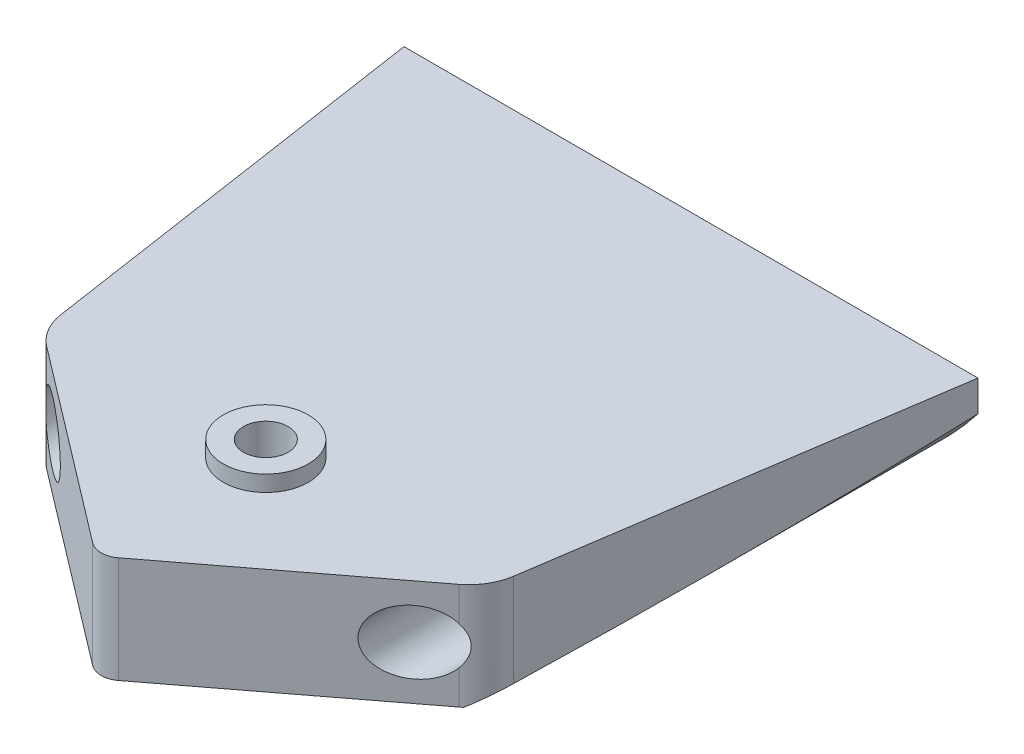
SolidWorks part; units mm, degrees
ref_plane "Front Plane" through (0, 0, 0) normal (0, 0, 1) x (1, 0, 0)
ref_plane "Top Plane" through (0, 0, 0) normal (0, 1, 0) x (1, 0, 0)
ref_plane "Right Plane" through (0, 0, 0) normal (1, 0, 0) x (0, 0, -1)
sketch "Sketch1" plane through (0, 0, 0) normal (0, 1, 0) x (1, 0, 0)
  line L0 (-21, 0) -> (21, 0) construction
  line L1 (-21, 0) -> (-21, 40) construction
  line L2 (21, 0) -> (21, 40) construction
  line L3 (21, 40) -> (-21, 40) construction
  line L4 (-19.3864, -1.2294) -> (-1.2121, -15.0765)
  line L5 (1.2121, -15.0765) -> (19.3864, -1.2294)
  line L6 (-27, 40) -> (-21.3009, 2.0061)
  line L7 (21.3009, 2.0061) -> (27, 40)
  line L8 (-27, 40) -> (27, 40)
  circle A0 centre (0, 0) radius 2.1
  circle A1 centre (0, 0) radius 4
  arc A2 (-21.3009, 2.0061) -> (-19.3864, -1.2294) centre (-16.3562, 2.7478) ccw
  arc A3 (21.3009, 2.0061) -> (19.3864, -1.2294) centre (16.3562, 2.7478) cw
  arc A4 (1.2121, -15.0765) -> (-1.2121, -15.0765) centre (0, -13.4856) cw
  point P7 (0, 0)
  point P22 (0, -16)
  dimension "D1" = 4.2
  dimension "D2" = 8
  dimension "D8" = 5
  dimension "D9" = 5
  dimension "D10" = 2
  dimension "D3" = 42
  dimension "D4" = 40
  dimension "D5" = 16
  dimension "D6" = 6
  dimension "D7" = 6
extrude "Boss-Extrude1" add sketch "Sketch1" along normal blind 10 contours A4 L5 A3 L7 L8 L6 A2 L4 A1 region at (0, 0, -17.3366)
extrude "Boss-Extrude2" add sketch "Sketch1<3>" along normal blind 11.5 contours A1 A0 region at (-3.8869, 0, 0)
sketch "Sketch1<3>" plane through (0, 0, 0) normal (0, 1, 0) x (1, 0, 0) same geometry as "Sketch1"
extrude "Cut-Extrude1" cut sketch "Sketch1<4>" along normal blind 3.5 contours A1 A0 region at (-3.8869, 0, 0)
sketch "Sketch1<4>" plane through (0, 0, 0) normal (0, 1, 0) x (1, 0, 0) same geometry as "Sketch1"
sketch "Sketch2" plane through (0, 0, -40) normal (0, 0, -1) x (-1, 0, 0)
  line L0 (-27, 10) -> (-27, 0) construction
  line L2 (27, 10) -> (-27, 10) construction
  line L9 (0, 0) -> (0, 10) construction
  circle A0 centre (-17, 5) radius 1.55
  circle A3 centre (17, 5) radius 1.55
  point P4 (-27, 5)
  dimension "D1" = 10
  dimension "D2" = 3.1
  dimension "D4" = 5
  dimension "D5" = 17
extrude "Cut-Extrude3" cut sketch "Sketch2" against normal blind 61.2 contours A0 | A3 region at (17, 5, -40) region at (-17, 5, -40)
sketch "Sketch3" plane through (0, 0, -40) normal (0, 0, -1) x (-1, 0, 0)
  line L0 (0, 11.5) -> (0, 27.75) construction
  line L1 (4, 11.5) -> (-4, 11.5) construction
  circle A0 centre (0, 27.75) radius 34
  circle A1 centre (0, 27.75) radius 51.2035
  dimension "D2" = 68
  dimension "D1" = 16.25
extrude "Cut-Extrude4" cut sketch "Sketch3" against normal through all
ref_plane "Plane1" through (0, 0, 20) normal (0, 0, -1) x (-1, 0, 0)
sketch "Sketch4" plane through (0, 0, 20) normal (0, 0, -1) x (-1, 0, 0)
  circle A0 centre (17, 5) radius 3
  circle A1 centre (-17, 5) radius 3
  dimension "D1" = 6
extrude "Cut-Extrude5" cut sketch "Sketch4" along normal blind 36
